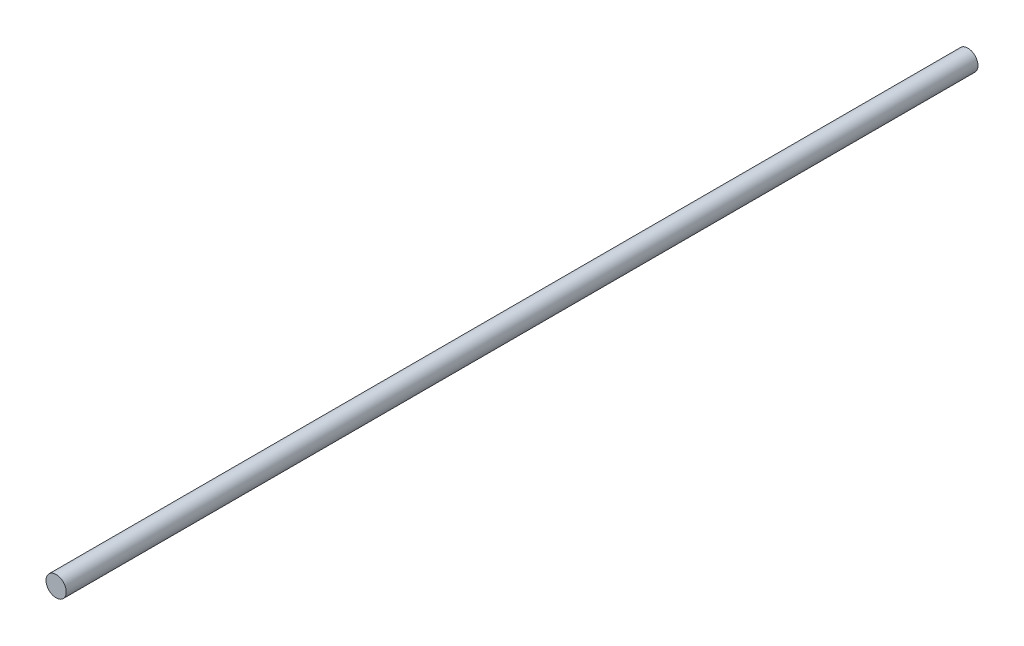
SolidWorks part; units mm, degrees
ref_plane "Спереди" through (0, 0, 0) normal (0, 0, 1) x (1, 0, 0)
ref_plane "Сверху" through (0, 0, 0) normal (0, 1, 0) x (1, 0, 0)
ref_plane "Справа" through (0, 0, 0) normal (1, 0, 0) x (0, 0, -1)
ref_plane "Плоскость4"
sketch "Эскиз1" plane through (0, 0, 0) normal (0, 0, 1) x (1, 0, 0)
  circle A0 centre (0, 0) radius 5
  dimension "D1" = 10
extrude "Выдавливание1" add sketch "Эскиз1" along normal blind 225 and the other way blind 225
